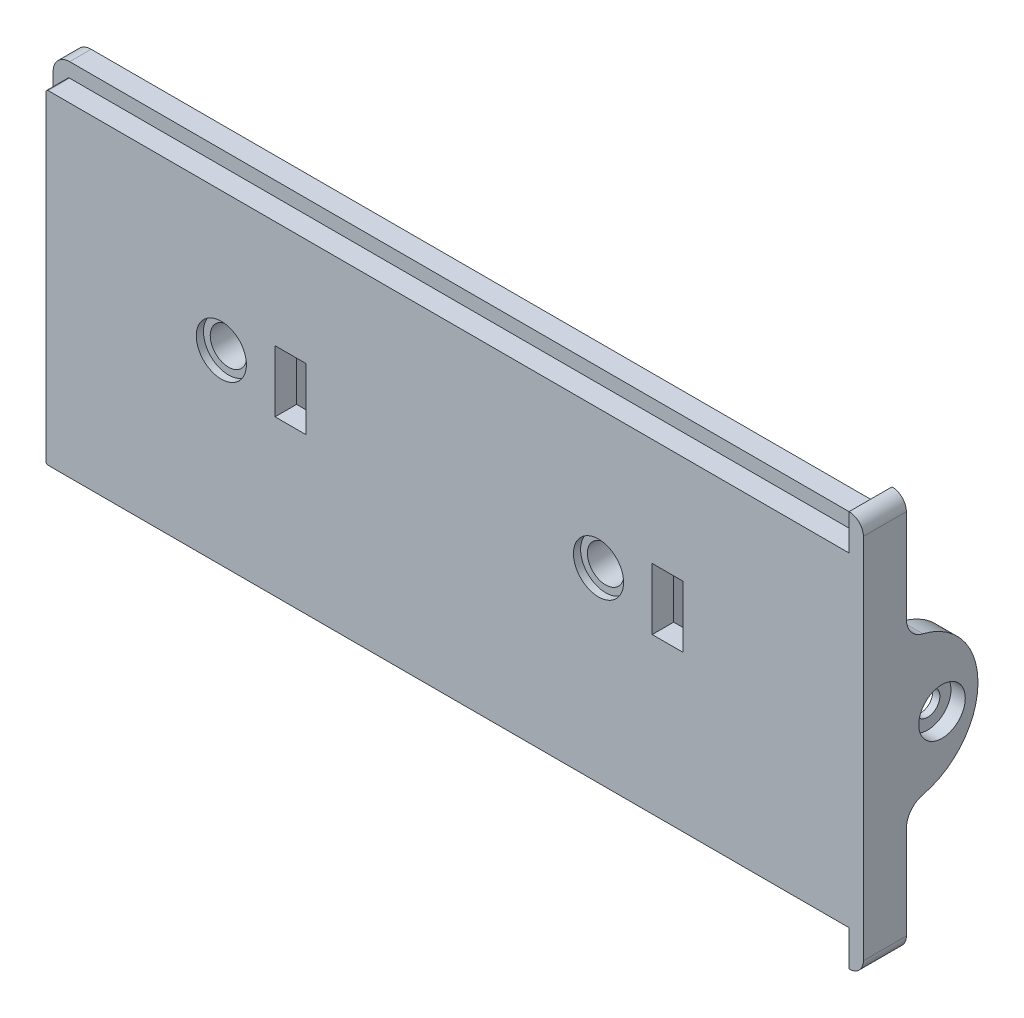
SolidWorks part; units mm, degrees
ref_plane "Front Plane" through (0, 0, 0) normal (0, 0, 1) x (1, 0, 0)
ref_plane "Top Plane" through (0, 0, 0) normal (0, 1, 0) x (1, 0, 0)
ref_plane "Right Plane" through (0, 0, 0) normal (1, 0, 0) x (0, 0, -1)
sketch "Sketch1" plane through (0, 0, 0) normal (0, 0, 1) x (1, 0, 0)
  line L0 (0, 26.65) -> (0, -26.65) construction
  line L1 (-54.25, 22.65) -> (-37.75, 22.65)
  line L2 (-54.55, 22.35) -> (-54.55, 12.1)
  line L3 (-54.25, -22.65) -> (-39.65, -22.65)
  line L4 (54.55, 22.35) -> (54.55, 12.1)
  line L5 (-54.55, 22.65) -> (54.55, -22.65) construction
  line L6 (-54.55, -22.65) -> (54.55, 22.65) construction
  line L15 (30.075, 7.65) -> (34.375, 7.65)
  line L32 (-7.55, 22.65) -> (7.55, 22.65)
  line L33 (37.75, 22.65) -> (54.25, 22.65)
  line L34 (-54.55, -18.1) -> (-54.55, -22.35)
  line L35 (-9.45, -22.65) -> (9.45, -22.65)
  line L36 (39.65, -22.65) -> (54.25, -22.65)
  line L37 (54.55, -18.1) -> (54.55, -22.35)
  line L38 (-22.575, 7.65) -> (-18.275, 7.65)
  line L39 (-22.575, 7.65) -> (-22.575, -0.95)
  line L40 (-22.575, -0.95) -> (-18.275, -0.95)
  line L41 (-18.275, 7.65) -> (-18.275, -0.95)
  line L42 (30.075, 7.65) -> (30.075, -0.95)
  line L43 (30.075, -0.95) -> (34.375, -0.95)
  line L44 (34.375, 7.65) -> (34.375, -0.95)
  line L45 (22.575, 3.35) -> (30.075, 3.35) construction
  line L47 (-49.65, -3) -> (55.45, -3) construction
  line L48 (-37.75, 22.65) -> (-7.55, 22.65)
  line L49 (7.55, 22.65) -> (37.75, 22.65)
  line L50 (54.55, 12.1) -> (54.55, -18.1)
  line L51 (9.45, -22.65) -> (39.65, -22.65)
  line L52 (-39.65, -22.65) -> (-9.45, -22.65)
  line L53 (-54.55, -18.1) -> (-54.55, 12.1)
  line L54 (-30.075, 3.35) -> (-22.575, 3.35) construction
  arc A0 (54.25, 22.65) -> (54.55, 22.35) centre (54.25, 22.35) cw
  arc A1 (54.25, -22.65) -> (54.55, -22.35) centre (54.25, -22.35) ccw
  arc A2 (-54.55, -22.35) -> (-54.25, -22.65) centre (-54.25, -22.35) ccw
  arc A3 (-54.25, 22.65) -> (-54.55, 22.35) centre (-54.25, 22.35) ccw
  circle A4 centre (-30.075, 3.35) radius 2.55
  circle A5 centre (22.575, 3.35) radius 2.55
  point P0 (0, 0)
  point P19 (-26.325, 3.35)
  point P20 (26.325, 3.35)
  dimension "D3" = 0.3
  dimension "D19" = 5.1
  dimension "D20" = 5.1
  dimension "D1" = 109.1
  dimension "D2" = 45.3
  dimension "D4" = 15
  dimension "D5" = 7.5
  dimension "D6" = 7.5
  dimension "D7" = 26.325
  dimension "D8" = 26.325
  dimension "D12" = 25.65
  dimension "D13" = 8.6
  dimension "D14" = 4.3
  dimension "D16" = 8.6
  dimension "D21" = 4.3
extrude "Boss-Extrude1" add sketch "Sketch1" along normal blind 3
sketch "Sketch2" plane through (0, 0, 3) normal (0, 0, 1) x (1, 0, 0)
  circle A0 centre (-30.075, 3.35) radius 3.5
  circle A1 centre (22.575, 3.35) radius 3.5
  dimension "D1" = 7
  dimension "D2" = 7
extrude "Cut-Extrude1" cut sketch "Sketch2" against normal blind 1
sketch "Sketch3" plane through (0, 0, 0) normal (0, 0, -1) x (-1, 0, 0)
  circle A0 centre (30.075, 3.35) radius 2.55 construction
  circle A1 centre (-22.575, 3.35) radius 2.55 construction
  circle A2 centre (30.075, 3.35) radius 2.55
  circle A3 centre (-22.575, 3.35) radius 2.55
  circle A4 centre (-22.575, 3.35) radius 3.55
  circle A5 centre (30.075, 3.35) radius 3.55
  dimension "D1" = 1
extrude "Boss-Extrude2" add sketch "Sketch3" along normal blind 5
sketch "Sketch7" plane through (0, 0, 0) normal (0, 0, -1) x (-1, 0, 0)
  line L1 (-26.525, 10.9) -> (-28.525, 10.9)
  line L2 (-26.525, 10.9) -> (-26.525, -4.1)
  line L3 (-26.525, -4.1) -> (-28.525, -4.1)
  line L4 (-28.525, 10.9) -> (-28.525, -4.1)
  line L6 (-37.925, 10.9) -> (-35.925, 10.9)
  line L7 (-37.925, 10.9) -> (-37.925, -4.1)
  line L8 (-37.925, -4.1) -> (-35.925, -4.1)
  line L9 (-35.925, 10.9) -> (-35.925, -4.1)
  line L10 (-34.375, 7.65) -> (-30.075, 7.65) construction
  line L13 (26.125, 10.9) -> (24.125, 10.9)
  line L14 (26.125, 10.9) -> (26.125, -4.1)
  line L15 (26.125, -4.1) -> (24.125, -4.1)
  line L16 (24.125, 10.9) -> (24.125, -4.1)
  line L17 (14.725, 10.9) -> (16.725, 10.9)
  line L18 (14.725, 10.9) -> (14.725, -4.1)
  line L19 (14.725, -4.1) -> (16.725, -4.1)
  line L20 (16.725, 10.9) -> (16.725, -4.1)
  line L22 (18.275, 7.65) -> (22.575, 7.65) construction
  point P4 (-32.225, 7.65)
  point P5 (20.425, 7.65)
  dimension "D1" = 15
  dimension "D2" = 2
  dimension "D3" = 2
  dimension "D4" = 3.25
  dimension "D5" = 15
  dimension "D6" = 2
  dimension "D7" = 2
  dimension "D8" = 3.25
  dimension "D9" = 7.4
  dimension "D10" = 7.4
  dimension "D11" = 3.7
  dimension "D12" = 3.7
extrude "Boss-Extrude4" add sketch "Sketch7" along normal blind 5
sketch "Sketch16" plane through (0, 0, 0) normal (0, 0, -1) x (-1, 0, 0)
  line L0 (54.25, 24.65) -> (-54.25, 24.65)
  line L1 (-56.55, 22.35) -> (-56.55, -22.35)
  line L2 (-54.25, -24.65) -> (54.25, -24.65)
  line L3 (56.55, -22.35) -> (56.55, 22.35)
  line L4 (-54.55, 22.35) -> (-54.55, -22.35)
  line L5 (-54.25, -22.65) -> (54.25, -22.65)
  line L6 (54.55, -22.35) -> (54.55, 22.35)
  line L7 (54.25, 22.65) -> (-54.25, 22.65)
  line L8 (-54.55, 22.35) -> (-54.55, -22.35) construction
  line L9 (-54.25, -22.65) -> (54.25, -22.65) construction
  line L10 (54.55, -22.35) -> (54.55, 22.35) construction
  line L11 (54.25, 22.65) -> (-54.25, 22.65) construction
  line L12 (53.05, 21.15) -> (-53.05, 21.15)
  line L13 (-53.05, 21.15) -> (-53.05, -21.15)
  line L14 (-53.05, -21.15) -> (53.05, -21.15)
  line L15 (53.05, -21.15) -> (53.05, 21.15)
  arc A0 (-54.25, 24.65) -> (-56.55, 22.35) centre (-54.25, 22.35) ccw
  arc A1 (-56.55, -22.35) -> (-54.25, -24.65) centre (-54.25, -22.35) ccw
  arc A2 (54.25, -24.65) -> (56.55, -22.35) centre (54.25, -22.35) ccw
  arc A3 (56.55, 22.35) -> (54.25, 24.65) centre (54.25, 22.35) ccw
  arc A4 (-54.25, 22.65) -> (-54.55, 22.35) centre (-54.25, 22.35) ccw
  arc A5 (-54.55, -22.35) -> (-54.25, -22.65) centre (-54.25, -22.35) ccw
  arc A6 (54.25, -22.65) -> (54.55, -22.35) centre (54.25, -22.35) ccw
  arc A7 (54.55, 22.35) -> (54.25, 22.65) centre (54.25, 22.35) ccw
  arc A8 (-54.25, 22.65) -> (-54.55, 22.35) centre (-54.25, 22.35) ccw construction
  arc A9 (-54.55, -22.35) -> (-54.25, -22.65) centre (-54.25, -22.35) ccw construction
  arc A10 (54.25, -22.65) -> (54.55, -22.35) centre (54.25, -22.35) ccw construction
  arc A11 (54.55, 22.35) -> (54.25, 22.65) centre (54.25, 22.35) ccw construction
  arc A12 (-53.05, 21.15) -> (-53.05, 21.15) centre (-53.05, 21.15) ccw
  arc A13 (-53.05, -21.15) -> (-53.05, -21.15) centre (-53.05, -21.15) ccw
  arc A14 (53.05, -21.15) -> (53.05, -21.15) centre (53.05, -21.15) ccw
  arc A15 (53.05, 21.15) -> (53.05, 21.15) centre (53.05, 21.15) ccw
  dimension "D1" = 0
  dimension "D2" = 2
  dimension "D3" = 1.5
extrude "Boss-Extrude9" add sketch "Sketch16" along normal blind 3
sketch "Sketch17" plane through (0, 0, 3) normal (0, 0, 1) x (1, 0, 0)
  line L0 (49.55, -24.65) -> (57.55, -24.65)
  line L2 (49.55, 24.65) -> (49.55, -24.65)
  line L4 (59.55, 24.65) -> (59.55, -24.65)
  line L5 (57.55, -24.65) -> (57.55, -27.65)
  line L6 (49.55, 24.65) -> (57.55, 24.65)
  line L7 (54.55, -22.35) -> (54.55, 22.35) construction
  line L8 (57.55, 24.65) -> (57.55, 27.65)
  line L11 (57.55, 27.65) -> (59.55, 27.65)
  line L12 (59.55, 24.65) -> (59.55, 27.65)
  line L15 (57.55, -27.65) -> (59.55, -27.65)
  line L16 (59.55, -24.65) -> (59.55, -27.65)
  line L17 (-54.25, 24.65) -> (54.25, 24.65) construction
  line L18 (54.25, -24.65) -> (-54.25, -24.65) construction
  line L19 (54.25, 22.65) -> (-54.25, 22.65) construction
  line L20 (-54.25, -22.65) -> (54.25, -22.65) construction
  dimension "D1" = 10
  dimension "D2" = 5
  dimension "D3" = 5
  dimension "D4" = 5
  dimension "D5" = 2
  dimension "D6" = 2
extrude "Boss-Extrude10" add sketch "Sketch17" against normal up to surface (6 mm away) up to face at (0, 0, -3)
fillet "Fillet1" radius 2 2 edges at (59.55, 27.65, 0) (59.55, -27.65, 0)
sketch "Sketch18" plane through (59.55, 0, 0) normal (1, 0, 0) x (0, 0, -1)
  line L0 (3, -25.65) -> (3, 25.65) construction
  line L1 (3, -10) -> (3, 10)
  arc A0 (3, -10) -> (3, 10) centre (3, 0) ccw
  dimension "D1" = 20
extrude "Boss-Extrude11" add sketch "Sketch18" against normal blind 3
fillet "Fillet2" radius 3 2 edges at (58.05, 10, -3) (58.05, -10, -3)
hole_wizard "CBORE for M3 Cheese Head Screw1" positions "3DSketch1" profile "Sketch19" counterbore size "M3" standard "AS" end condition up to next
sketch3d "3DSketch1"
  line L4 (59.55, -0.995, -12.9504) -> (59.55, -0.995, -3) construction
  line L5 (59.55, -12.6491, -3) -> (59.55, 12.6491, -3) construction
  arc A0 (59.55, -9.7301, -5.3077) -> (59.55, 9.7301, -5.3077) centre (59.55, 0, -3) ccw construction
  point P0 (59.55, -0.995, -7.9752)
  point P17 (69.55, 0, -3)
  point P21 (59.55, -0.995, -7.9752)
sketch "Sketch19" plane through (59.55, -0.995, -7.9752) normal (0, 1, 0) x (0, 0, -1)
  line L0 (0, 0) -> (0, 3)
  line L1 (0, 3) -> (1.7, 3)
  line L3 (1.7, 3) -> (1.7, 2)
  line L4 (1.7, 2) -> (3.25, 2)
  line L5 (3.25, 2) -> (3.25, 0)
  line L7 (3.25, 0) -> (0, 0)
  line L11 (0, -6.35) -> (0, 107.95) construction
  dimension "Thru Hole Dia." = 3.4
  dimension "Thru Hole Depth" = 3
  dimension "C'Bore Dia." = 6.5
  dimension "C'Bore Depth" = 2
sketch "Sketch20" plane through (49.55, 0, 0) normal (-1, 0, 0) x (0, 0, 1)
  line L0 (3, -22.65) -> (0, -22.65) construction
  line L1 (0, -22.65) -> (0, -24.65) construction
  line L2 (0, -24.65) -> (3, -24.65) construction
  line L3 (3, -24.65) -> (3, -22.65) construction
  line L4 (0, 22.65) -> (3, 22.65) construction
  line L5 (3, 22.65) -> (3, 24.65) construction
  line L6 (3, 24.65) -> (0, 24.65) construction
  line L7 (0, 24.65) -> (0, 22.65) construction
  line L8 (3, -22.65) -> (0, -22.65)
  line L9 (0, -22.65) -> (0, -24.65)
  line L10 (0, -24.65) -> (3, -24.65)
  line L11 (3, -24.65) -> (3, -22.65)
  line L12 (0, 22.65) -> (3, 22.65)
  line L13 (3, 22.65) -> (3, 24.65)
  line L14 (3, 24.65) -> (0, 24.65)
  line L15 (0, 24.65) -> (0, 22.65)
extrude "Cut-Extrude3" cut sketch "Sketch20" against normal up to surface (8 mm away) up to face at (57.55, 26.15, 0)
